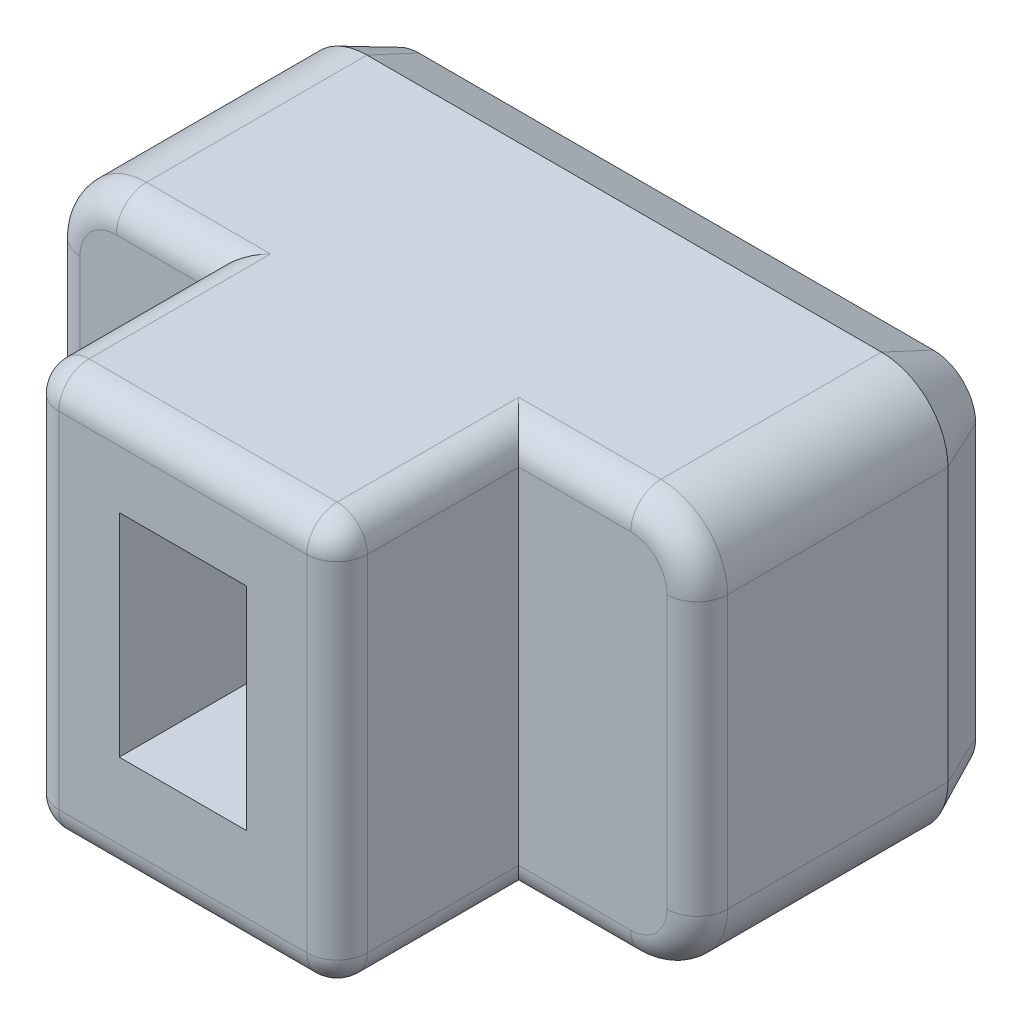
SolidWorks part; units mm, degrees
ref_plane "Plan de face" through (0, 0, 0) normal (0, 0, 1) x (1, 0, 0)
ref_plane "Plan de dessus" through (0, 0, 0) normal (0, 1, 0) x (1, 0, 0)
ref_plane "Plan de droite" through (0, 0, 0) normal (1, 0, 0) x (0, 0, -1)
sketch "Esquisse2" plane through (0, 0, 0) normal (0, 0, 1) x (1, 0, 0)
  line L1 (1.1, 0) -> (9.6, 0)
  line L2 (0, 1.1) -> (0, 5.6)
  line L3 (1.1, 6.7) -> (9.6, 6.7)
  line L4 (10.7, 1.1) -> (10.7, 5.6)
  arc A0 (9.6, 6.7) -> (10.7, 5.6) centre (9.6, 5.6) cw
  arc A1 (9.6, 0) -> (10.7, 1.1) centre (9.6, 1.1) ccw
  arc A2 (1.1, 0) -> (0, 1.1) centre (1.1, 1.1) cw
  arc A3 (0, 5.6) -> (1.1, 6.7) centre (1.1, 5.6) cw
  point P7 (10.7, 6.7)
  point P12 (0, 0)
  point P15 (0, 6.7)
  dimension "D3" = 1.1
  dimension "D1" = 10.7
  dimension "D2" = 6.7
extrude "Boss.-Extru.1" add sketch "Esquisse2" along normal blind 8
sketch "Esquisse3" plane through (0, 0, 8) normal (0, 0, 1) x (1, 0, 0)
  line L0 (0, 5.6) -> (0, 1.1) construction
  line L1 (4.15, 5.25) -> (6.25, 5.25)
  line L2 (4.15, 5.25) -> (4.15, 1.75)
  line L3 (4.15, 1.75) -> (6.25, 1.75)
  line L4 (6.25, 5.25) -> (6.25, 1.75)
  line L5 (10.7, 1.1) -> (10.7, 5.6) construction
  line L6 (9.6, 6.7) -> (1.1, 6.7) construction
  line L7 (1.1, 0) -> (9.6, 0) construction
  dimension "D1" = 2.1
  dimension "D2" = 3.5
  dimension "D3" = 4.15
  dimension "D4" = 4.45
  dimension "D5" = 1.45
  dimension "D6" = 1.75
extrude "Enlèv. mat.-Extru.1" cut sketch "Esquisse3" against normal blind 3
sketch "Esquisse4" plane through (0, 0, 8) normal (0, 0, 1) x (1, 0, 0)
  line L0 (2.65, 6.7) -> (2.65, 0)
  line L1 (9.6, 6.7) -> (1.1, 6.7) construction
  line L2 (1.1, 0) -> (9.6, 0) construction
  line L3 (2.65, 0) -> (7.75, 0)
  line L4 (7.75, 0) -> (7.75, 6.7)
  line L5 (7.75, 6.7) -> (2.65, 6.7)
  line L6 (4.15, 5.25) -> (4.15, 1.75) construction
  line L7 (6.25, 1.75) -> (6.25, 5.25) construction
  dimension "D1" = 1.5
  dimension "D2" = 1.5
extrude "Enlèv. mat.-Extru.2" cut sketch "Esquisse4" against normal blind 3 flip side to cut
fillet "Congé1" radius 0.5 18 edges at (8.675, 0, 5) (10.3778, 0.3222, 5) (10.7, 3.35, 5) (10.3778, 6.3778, 5) (1.875, 6.7, 5) (0.3222, 6.3778, 5) (1.875, 0, 5) (0.3222, 0.3222, 5) (7.75, 6.7, 6.5) (2.65, 6.7, 6.5) (7.75, 0, 6.5) (2.65, 0, 6.5) (2.65, 3.35, 8) (5.2, 6.7, 8) (7.75, 3.35, 8) (5.2, 0, 8) (8.675, 6.7, 5) (0, 3.35, 5)
chamfer "Chanfrein1" distance 0.4 angle 65 8 edges at (5.35, 0, 0) (10.3778, 0.3222, 0) (0.3222, 0.3222, 0) (10.7, 3.35, 0) (0, 3.35, 0) (10.3778, 6.3778, 0) (0.3222, 6.3778, 0) (5.35, 6.7, 0) first distance on face at (5.35, 3.35, 0)
sketch "Esquisse5" plane through (0, 0, 0) normal (0, 0, 1) x (1, 0, 0)
  line L0 (-0.9378, 5.093) -> (11.6517, 5.093) construction
  text T0 "MENU" font "Corbel" height 3.5
extrude "Enlèv. mat.-Extru.3" cut sketch "Esquisse5" along normal blind 0.2
extrude "Boss.-Extru.2" add sketch "Esquisse5<4>" against normal blind 0.2
sketch "Esquisse5<4>" plane through (0, 0, 0) normal (0, 0, 1) x (1, 0, 0) same geometry as "Esquisse5"
